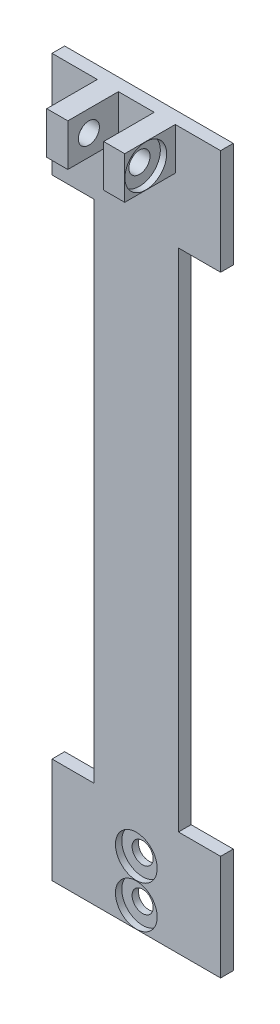
SolidWorks part; units mm, degrees
ref_plane "Front Plane" through (0, 0, 0) normal (0, 0, 1) x (1, 0, 0)
ref_plane "Top Plane" through (0, 0, 0) normal (0, 1, 0) x (1, 0, 0)
ref_plane "Right Plane" through (0, 0, 0) normal (1, 0, 0) x (0, 0, -1)
sketch "Sketch1" plane through (0, 0, 0) normal (0, 0, 1) x (1, 0, 0)
  line L0 (-14.0259, 115.3035) -> (-14.0259, -54.6965) construction
  line L1 (-34.0259, 115.3035) -> (5.9741, 115.3035)
  line L2 (-34.0259, 115.3035) -> (-34.0259, -54.6965)
  line L3 (-34.0259, -54.6965) -> (5.9741, -54.6965)
  line L4 (5.9741, 115.3035) -> (5.9741, -54.6965)
  line L5 (-24.0259, 30.3035) -> (-34.0259, 30.3035) construction
  line L6 (-34.0259, 90.3035) -> (-24.0259, 90.3035)
  line L7 (-34.0259, 90.3035) -> (-34.0259, -29.6965)
  line L8 (-34.0259, -29.6965) -> (-24.0259, -29.6965)
  line L9 (-24.0259, 90.3035) -> (-24.0259, -29.6965)
  line L10 (5.9741, 30.3035) -> (-34.0259, 30.3035) construction
  line L11 (5.9741, 90.3035) -> (-4.0259, 90.3035)
  line L12 (-4.0259, 90.3035) -> (-4.0259, -29.6965)
  line L13 (5.9741, -29.6965) -> (-4.0259, -29.6965)
  line L14 (-14.0259, 105.3035) -> (-14.0259, 115.3035) construction
  line L15 (-18.2759, 115.3035) -> (-9.7759, 115.3035)
  line L16 (-18.2759, 115.3035) -> (-18.2759, 105.3035)
  line L17 (-18.2759, 105.3035) -> (-9.7759, 105.3035)
  line L18 (-9.7759, 115.3035) -> (-9.7759, 105.3035)
  line L20 (-18.2759, 105.3035) -> (-23.2759, 105.3035)
  line L21 (-18.2759, 105.3035) -> (-18.2759, 115.3035)
  line L22 (-18.2759, 115.3035) -> (-23.2759, 115.3035)
  line L23 (-23.2759, 105.3035) -> (-23.2759, 115.3035)
  line L24 (-9.7759, 105.3035) -> (-4.7759, 105.3035)
  line L25 (-9.7759, 105.3035) -> (-9.7759, 115.3035)
  line L26 (-9.7759, 115.3035) -> (-4.7759, 115.3035)
  line L27 (-4.7759, 105.3035) -> (-4.7759, 115.3035)
  circle A0 centre (-14.0259, -49.6965) radius 2.5
  circle A1 centre (-14.0259, -39.6965) radius 2.5
  circle A2 centre (-14.0259, -39.6965) radius 4.95
  circle A3 centre (-14.0259, -49.6965) radius 4.95
  dimension "D3" = 5
  dimension "D4" = 5
  dimension "D5" = 9.9
  dimension "D6" = 9.9
  dimension "D1" = 170
  dimension "D2" = 40
  dimension "D7" = 5
  dimension "D8" = 15
  dimension "D9" = 120
  dimension "D10" = 10
  dimension "D11" = 10
  dimension "D12" = 8.5
  dimension "D13" = 5
  dimension "D14" = 5
extrude "Body" add sketch "Sketch1" along normal blind 3 contours L27 L24 L17 L20 L23 L1 L2 L6 L9 L8 L3 L4 L13 L12 L11 A3 A2 | L23 L20 L16 L1 | L18 L1 L16 L17 | L24 L27 L1 L18 region at (-14.0259, 29.5024, 0) region at (-20.7759, 110.3035, 0) region at (-14.0259, 110.3035, 0) region at (-7.2759, 110.3035, 0)
extrude "Mount Insets" add sketch "Sketch1<3>" along normal blind 1.5 contours A2 A1 | A3 A0 region at (-18.8359, -39.6965, 0) region at (-18.8359, -49.6965, 0)
sketch "Sketch1<3>" plane through (0, 0, 0) normal (0, 0, 1) x (1, 0, 0) same geometry as "Sketch1"
extrude "Hinge" add sketch "Sketch1<5>" along normal blind 15 contours L24 L27 L1 L18 | L20 L23 L22 L21 region at (-7.2759, 110.3035, 0)
sketch "Sketch1<5>" plane through (0, 0, 0) normal (0, 0, 1) x (1, 0, 0) same geometry as "Sketch1"
sketch "Sketch2" plane through (-4.7759, 0, 0) normal (1, 0, 0) x (0, 0, -1)
  line L0 (-15, 110.3035) -> (-3, 110.3035) construction
  line L1 (-15, 105.3035) -> (-15, 115.3035) construction
  line L2 (-3, 115.3035) -> (-3, 105.3035) construction
  line L3 (-10, 115.3035) -> (-10, 105.3035) construction
  line L4 (-15, 115.3035) -> (-3, 115.3035) construction
  line L5 (-15, 105.3035) -> (-3, 105.3035) construction
  circle A0 centre (-10, 110.3035) radius 2.5
  circle A1 centre (-10, 110.3035) radius 4.95
  dimension "D2" = 5
  dimension "D3" = 9.9
  dimension "D1" = 5
extrude "Hinge Inset" cut sketch "Sketch2" against normal blind 1.5
extrude "Hinge Inset2" cut sketch "Sketch2<2>" along normal blind 1.5 from surface starting at face at (-23.2759, 110.3035, 9)
sketch "Sketch2<2>" plane through (-4.7759, 0, 0) normal (1, 0, 0) x (0, 0, -1) same geometry as "Sketch2"
extrude "Hinge Screwhole" cut sketch "Sketch2<3>" against normal through all contours A0 region at (-4.7759, 110.3035, 10)
sketch "Sketch2<3>" plane through (-4.7759, 0, 0) normal (1, 0, 0) x (0, 0, -1) same geometry as "Sketch2"
